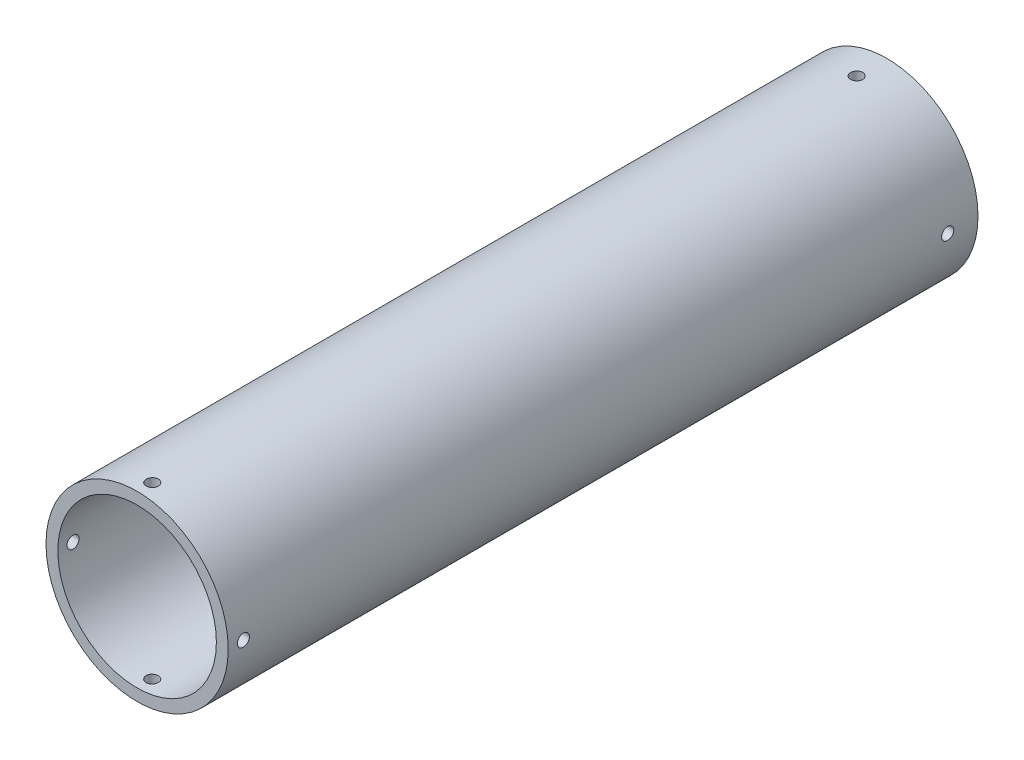
SolidWorks part; units mm, degrees
material "6061 Alloy"
ref_plane "Front Plane" through (0, 0, 0) normal (0, 0, 1) x (1, 0, 0)
ref_plane "Top Plane" through (0, 0, 0) normal (0, 1, 0) x (1, 0, 0)
ref_plane "Right Plane" through (0, 0, 0) normal (1, 0, 0) x (0, 0, -1)
sketch "Sketch1" plane through (0, 0, 0) normal (0, 0, 1) x (1, 0, 0)
  circle A0 centre (0, 0) radius 26.1874
  circle A1 centre (0, 0) radius 30.099
  dimension "D1" = 52.3748
  dimension "D2" = 60.198
extrude "Boss-Extrude1" add sketch "Sketch1" along normal blind 247.7
ref_plane "Plane1" through (0, 0, 10) normal (0, 0, -1) x (-1, 0, 0)
hole_wizard "Ø4.0mm Dowel Hole1" positions "3DSketch1" profile "Sketch2" hole size "Ø4.0" standard "ISO"
sketch3d "3DSketch1"
  line L0 (-30.099, 0, 10) -> (30.099, 0, 10)
  line L2 (0, -30.099, 10) -> (0, 30.099, 10)
  point P0 (0, 30.099, 10)
  point P2 (30.099, 0, 10)
  point P4 (0, -30.099, 10)
  point P6 (-30.099, 0, 10)
  dimension "D1" = 0
sketch "Sketch2" plane through (0, 30.099, 10) normal (1, 0, 0) x (0, 0, 1)
  line L0 (0, 0) -> (0, 7.2017)
  line L1 (0, 7.2017) -> (2, 6)
  line L2 (2, 6) -> (2, 0)
  line L5 (2, 0) -> (0, 0)
  line L10 (0, 7.2017) -> (-2, 6) construction
  line L11 (0, -6.35) -> (0, 107.95) construction
  dimension "Hole Dia." = 4
  dimension "Hole Depth" = 6
  dimension "Drill Angle" = 118
ref_plane "Plane2" through (0, 0, 242.7) normal (0, 0, 1) x (1, 0, 0)
hole_wizard "Ø4.0mm Dowel Hole2" positions "3DSketch2" profile "Sketch3" hole size "Ø4.0" standard "ISO"
sketch3d "3DSketch2"
  line L0 (30.099, 0, 242.7) -> (-30.099, 0, 242.7)
  line L2 (0, -30.099, 242.7) -> (0, 30.099, 242.7)
  point P0 (0, -30.099, 242.7)
  point P2 (-30.099, 0, 242.7)
  point P4 (0, 30.099, 242.7)
  point P6 (30.099, 0, 242.7)
  dimension "D1" = 0
sketch "Sketch3" plane through (0, -30.099, 242.7) normal (1, 0, 0) x (0, 0, -1)
  line L0 (0, 0) -> (0, 7.2017)
  line L1 (0, 7.2017) -> (2, 6)
  line L2 (2, 6) -> (2, 0)
  line L5 (2, 0) -> (0, 0)
  line L10 (0, 7.2017) -> (-2, 6) construction
  line L11 (0, -6.35) -> (0, 107.95) construction
  dimension "Hole Dia." = 4
  dimension "Hole Depth" = 6
  dimension "Drill Angle" = 118
